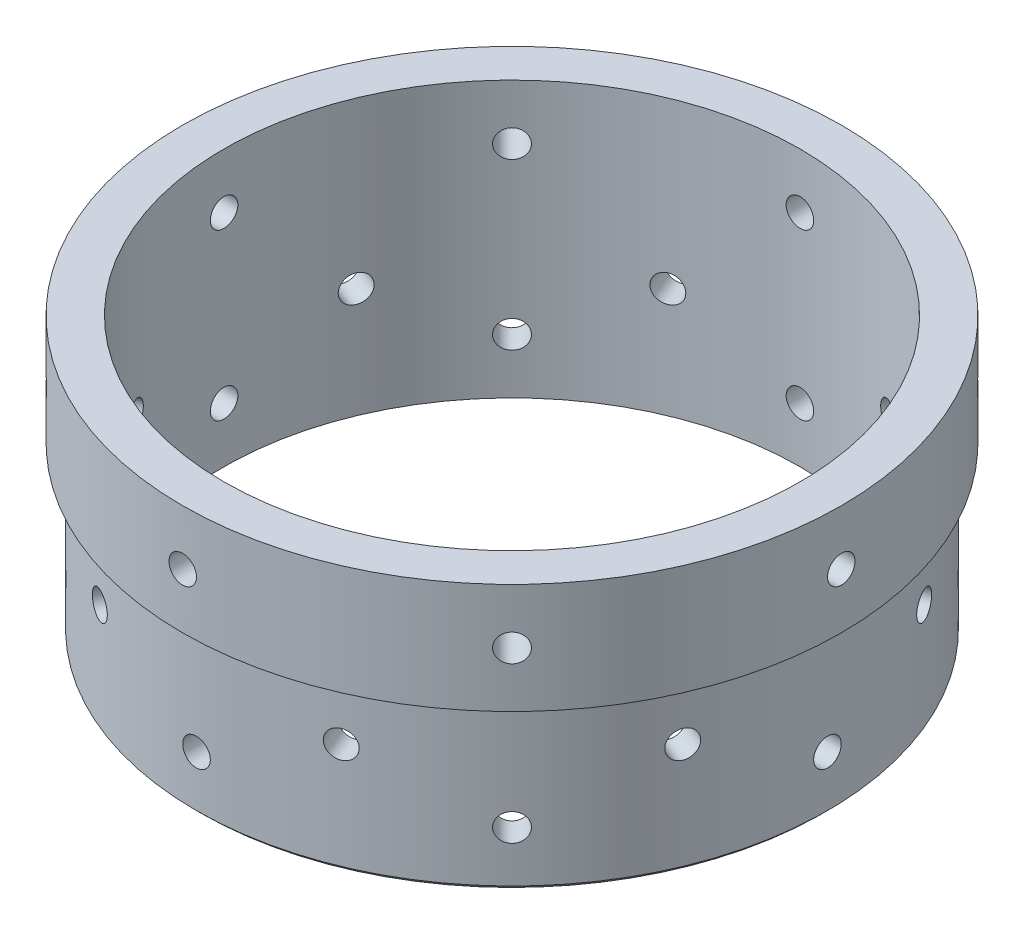
SolidWorks part; units mm, degrees
material "6061-T6 (SS)"
ref_plane "Front Plane" through (0, 0, 0) normal (0, 0, 1) x (1, 0, 0)
ref_plane "Top Plane" through (0, 0, 0) normal (0, 1, 0) x (1, 0, 0)
ref_plane "Right Plane" through (0, 0, 0) normal (1, 0, 0) x (0, 0, -1)
sketch "Sketch1" plane through (0, 0, 0) normal (0, 1, 0) x (1, 0, 0)
  circle A0 centre (0, 0) radius 66.4845
  circle A1 centre (0, 0) radius 76.0095
  circle A2 centre (0, 0) radius 72.8345
  dimension "D1" = 152.019
  dimension "D2" = 3.175
  dimension "D3" = 6.35
extrude "Boss-Extrude1" add sketch "Sketch1" along normal blind 25.4 contours A2 A0 | A1 A2 region at (-73.8596, 0, 0) region at (-70.7744, 0, 0)
extrude "Boss-Extrude2" add sketch "Sketch1<3>" against normal blind 38.1 contours A2 A0 region at (-70.7744, 0, 0)
sketch "Sketch1<3>" plane through (0, 0, 0) normal (0, 1, 0) x (1, 0, 0) same geometry as "Sketch1"
sketch "Sketch2" plane through (0, 0, 0) normal (0, 0, 1) x (1, 0, 0)
  line L0 (0, 0) -> (0, 12.7) construction
  line L1 (0, 0) -> (0, -25.4) construction
  circle A0 centre (0, 12.7) radius 3.175
  circle A1 centre (0, -25.4) radius 3.175
  dimension "D1" = 6.35
  dimension "D2" = 6.35
  dimension "D4" = 12.7
  dimension "D3" = 25.4
extrude "Cut-Extrude1" cut sketch "Sketch2" against normal through all
chamfer "Chamfer1" distance 1 angle 45 1 edges at (0, -38.1, 72.8345)
pattern_circular "CirPattern1" count 8 over 360 about axis through (0, 25.4, 0) along (0, -1, 0) of "Cut-Extrude1"
ref_plane "Plane1" through (-29.0876, 0, 70.2236) normal (-0.3827, 0, 0.9239) x (0, -1, 0)
sketch "Sketch3" plane through (-29.0876, 0, 70.2236) normal (-0.3827, 0, 0.9239) x (0, -1, 0)
  line L0 (12.7, 0) -> (0, 0) construction
  circle A0 centre (12.7, 0) radius 3.175
  dimension "D1" = 6.35
  dimension "D2" = 12.7
extrude "Cut-Extrude2" cut sketch "Sketch3" against normal blind 38.1
pattern_circular "CirPattern2" count 8 over 360 about axis through (0, 25.4, 0) along (0, -1, 0) of "Cut-Extrude2" reverse direction yes
